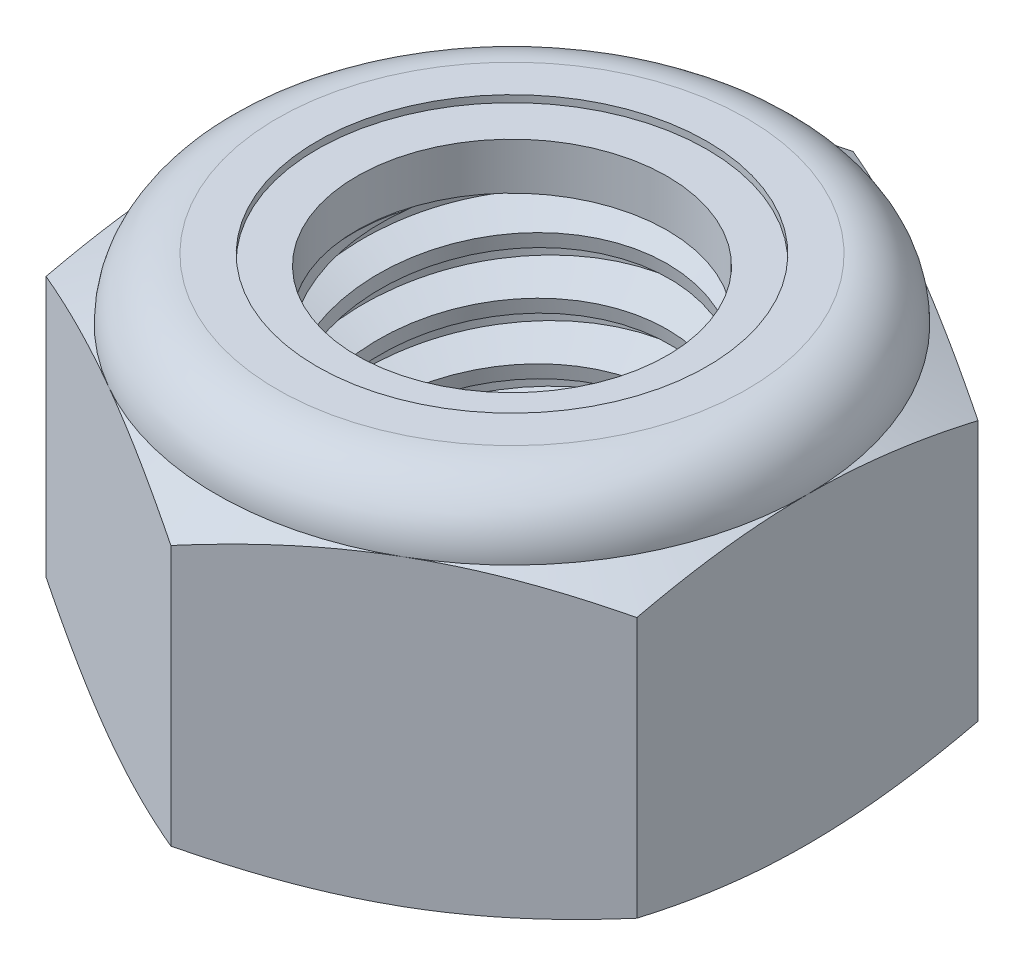
SolidWorks part; units mm, degrees
ref_plane "Front" through (0, 0, 0) normal (0, 0, 1) x (1, 0, 0)
ref_plane "Top" through (0, 0, 0) normal (0, 1, 0) x (1, 0, 0)
ref_plane "Right" through (0, 0, 0) normal (1, 0, 0) x (0, 0, -1)
sketch "Sketch1" plane through (0, 0, 0) normal (0, 1, 0) x (1, 0, 0)
  line L1 (0, 7.5056) -> (-6.5, 3.7528)
  line L2 (-6.5, 3.7528) -> (-6.5, -3.7528)
  line L3 (-6.5, -3.7528) -> (0, -7.5056)
  line L4 (0, -7.5056) -> (6.5, -3.7528)
  line L5 (6.5, -3.7528) -> (6.5, 3.7528)
  line L6 (6.5, 3.7528) -> (0, 7.5056)
  circle A0 centre (0, 0) radius 6.5 construction
  dimension "Hex Flats" = 13
extrude "Extrude1" add sketch "Sketch1" along normal blind 8
sketch "Sketch2" plane through (0, 0, 0) normal (1, 0, 0) x (0, 0, -1)
  line L0 (-4, 0) -> (-4, 8) construction
  line L1 (0, 0) -> (4, 0)
  line L2 (0, 0) -> (0, 8)
  line L3 (0, 8) -> (4, 8)
  line L4 (4, 0) -> (4, 8)
  line L5 (-3.7528, 8) -> (3.7528, 8) construction
  line L7 (0, -4) -> (0, 0) construction
  dimension "Thread Dia" = 8
revolve "Revolve1" add sketch "Sketch2" angle 360 about L7
sketch "Sketch3" plane through (0, 0, 0) normal (1, 0, 0) x (0, 0, -1)
  line L0 (4, 8) -> (-4, 8) construction
  line L1 (-4, 8) -> (-4, 6.75) construction
  line L2 (-4, 6.75) -> (4, 8) construction
  line L3 (4, 8) -> (4.0241, 7.8456) construction
  line L4 (4.0241, 7.8456) -> (4.193, 6.765)
  line L5 (4.193, 6.765) -> (3.4642, 7.0465)
  line L6 (3.4642, 7.0465) -> (3.416, 7.3552)
  line L7 (3.416, 7.3552) -> (4.0241, 7.8456)
  line L8 (3.4401, 7.2009) -> (4.1085, 7.3053) construction
  line L9 (4, 8) -> (4, 7.2883) construction
  line L10 (4, 7.2883) -> (-4, 6.0383) construction
  line L11 (-4, 6.0383) -> (-4, 6.75) construction
  line L12 (-0.2089, 8) -> (0.2089, 5.3267) construction
  line L13 (-4, 0) -> (-4, 8) construction
  line L14 (0, 8) -> (4, 8) construction
  line L15 (4, 0) -> (4, 8) construction
  point P13 (0, 6.6633)
  dimension "D1" = 0.1562
  dimension "D2" = 0.3125
  dimension "Thread Pitch" = 1.25
  dimension "D4" = 60
  dimension "D5" = 1.25
revolve "Cut-Revolve1" cut sketch "Sketch3" angle 360 about L12
pattern_linear "LPattern1" count 6 spacing 1.25 along (0, -1, 0) count 2 spacing 1.25 along (0, 1, 0) of "Cut-Revolve1"
sketch "Sketch4" plane through (0, 0, 0) normal (1, 0, 0) x (0, 0, -1)
  line L0 (0, 8) -> (4, 8)
  line L1 (4, 8) -> (3.416, 7.7277)
  line L2 (3.416, 7.7277) -> (3.416, 0.2723)
  line L3 (3.416, 0.2723) -> (4, 0)
  line L4 (4, 0) -> (0, 0)
  line L5 (0, 0) -> (0, 8)
  line L6 (4, 0) -> (4, 8) construction
  line L7 (0, 8) -> (4, 8) construction
  line L8 (0, 0) -> (4, 0) construction
  line L9 (0, 0) -> (0, 8) construction
  line L10 (0, 8) -> (0, 8.6444) construction
  dimension "D1" = 25
revolve "Cut-Revolve2" cut sketch "Sketch4" angle 360 about L10
combine bodies "Combine1" operation type subtract main body 112 bodies to subtract 111
sketch "Sketch5" plane through (0, 0, 0) normal (1, 0, 0) x (0, 0, -1)
  line L0 (0, 0) -> (6.5, 0)
  line L1 (6.5, 0) -> (7.5056, 0.4689)
  line L2 (7.5056, 0.4689) -> (7.5056, 6.1978)
  line L3 (7.5056, 6.1978) -> (6.5, 6.6667)
  line L4 (5.1667, 8) -> (5.1667, 9.27)
  line L5 (5.1667, 9.27) -> (8.7756, 9.27)
  line L6 (8.7756, 9.27) -> (8.7756, -1.27)
  line L7 (8.7756, -1.27) -> (0, -1.27)
  line L8 (0, -1.27) -> (0, 0)
  line L9 (6.5, 6.6667) -> (6.5, 0) construction
  line L10 (0, 0) -> (4, 0) construction
  line L13 (7.5056, 3.3333) -> (8.7756, 3.3333) construction
  line L14 (7.5056, 8) -> (7.5056, 0) construction
  line L15 (0, 0) -> (0, 9.27) construction
  line L20 (0, 9.27) -> (5.1667, 9.27) construction
  line L22 (0, 8) -> (4, 8) construction
  arc A0 (6.5, 6.6667) -> (5.1667, 8) centre (5.1667, 6.6667) ccw
  dimension "D1" = 25
  dimension "D2" = 1.27
  dimension "D3" = 8
  dimension "D4" = 1.3333
revolve "Cut-Revolve3" cut sketch "Sketch5" angle 360 about L15
sketch "Sketch6" plane through (0, 0, 0) normal (1, 0, 0) x (0, 0, -1)
  line L0 (0, 6.6667) -> (6.3476, 6.6667)
  line L1 (5.1667, 7.8476) -> (4.2913, 7.8476)
  line L2 (0, 9.27) -> (0, 6.6667)
  line L3 (4.2913, 9.27) -> (0, 9.27)
  line L4 (0, 9.27) -> (5.1667, 9.27) construction
  line L5 (0, 0) -> (0, 9.27) construction
  line L6 (0, 9.27) -> (0, 44.323) construction
  line L7 (4.2913, 7.8476) -> (4.2913, 9.27)
  line L8 (5.1667, 8) -> (5.1667, 7.8476) construction
  line L9 (4.2913, 7.8476) -> (3.416, 7.8476) construction
  line L10 (3.416, 7.8476) -> (3.416, 7.7277) construction
  arc A0 (6.3476, 6.6667) -> (5.1667, 7.8476) centre (5.1667, 6.6667) ccw
  arc A1 (6.5, 6.6667) -> (5.1667, 8) centre (5.1667, 6.6667) ccw construction
  dimension "D1" = 0.1524
revolve "Cut-Revolve4" cut sketch "Sketch6" angle 360 about L6
sketch "Sketch7" plane through (0, 0, 0) normal (1, 0, 0) x (0, 0, -1)
  line L0 (3.416, 6.7429) -> (6.2688, 6.7429)
  line L1 (5.1667, 7.7714) -> (3.416, 7.7714)
  line L2 (3.416, 7.7714) -> (3.416, 6.7429)
  line L3 (3.416, 6.7429) -> (0, 6.7429) construction
  line L4 (0, 6.7429) -> (0, 7.7714) construction
  line L5 (0, 7.7714) -> (3.416, 7.7714) construction
  line L6 (3.416, 6.7429) -> (3.416, 6.6667) construction
  line L7 (0, 6.6667) -> (6.3476, 6.6667) construction
  line L8 (5.1667, 7.7714) -> (5.1667, 7.8476) construction
  arc A0 (6.2688, 6.7429) -> (5.1667, 7.7714) centre (5.1667, 6.6667) ccw
  arc A2 (6.3476, 6.6667) -> (5.1667, 7.8476) centre (5.1667, 6.6667) ccw construction
  dimension "D1" = 0.0762
revolve "Revolve2" add sketch "Sketch7" angle 360 about L4
equation "\"D1@Sketch3\"=\"Thread Pitch@Sketch3\"/8"
equation "\"D2@Sketch3\"=\"Thread Pitch@Sketch3\"/4"
equation "\"D5@Sketch3\"=\"Thread Pitch@Sketch3\""
equation "\"D4@LPattern1\"=\"Thread Pitch@Sketch3\""
equation "\"D3@LPattern1\"=\"Thread Pitch@Sketch3\""
equation "\"D1@LPattern1\"=\"Height@Extrude1\"/\"Thread Pitch@Sketch3\""
equation "\"D4@Sketch5\"=\"Height@Extrude1\"/6"
